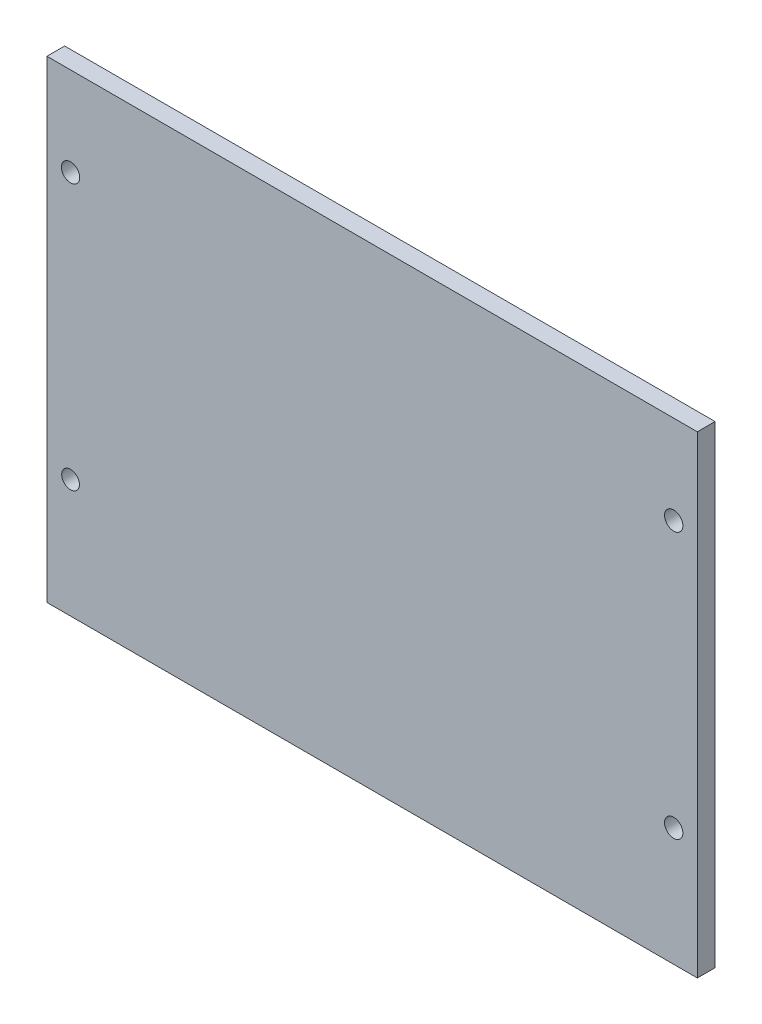
SolidWorks part; units mm, degrees
ref_plane "前视基准面" through (0, 0, 0) normal (0, 0, 1) x (1, 0, 0)
ref_plane "上视基准面" through (0, 0, 0) normal (0, 1, 0) x (1, 0, 0)
ref_plane "右视基准面" through (0, 0, 0) normal (1, 0, 0) x (0, 0, -1)
other "Configuration Table"
sketch "草图1" plane through (0, 0, 0) normal (0, 0, 1) x (1, 0, 0)
  line L1 (55, -40) -> (-55, -40)
  line L2 (55, -40) -> (55, 40)
  line L3 (55, 40) -> (-55, 40)
  line L4 (-55, -40) -> (-55, 40)
  line L5 (55, -40) -> (-55, 40) construction
  line L6 (55, 40) -> (-55, -40) construction
  point P0 (0, 0)
  dimension "D1" = 80
  dimension "D2" = 110
extrude "凸台-拉伸1" add sketch "草图1" along normal blind 3
sketch "草图2" plane through (0, 0, 3) normal (0, 0, 1) x (1, 0, 0)
  line L0 (55, 40) -> (-55, 40) construction
  line L1 (-55, 40) -> (-55, -40) construction
  line L2 (55, -40) -> (55, 40) construction
  line L3 (-55, -40) -> (55, -40) construction
  circle A0 centre (51, 25) radius 1.55
  circle A1 centre (51, -20) radius 1.55
  circle A2 centre (-51, 25) radius 1.55
  circle A3 centre (-51, -20) radius 1.5
  dimension "D1" = 15
  dimension "D2" = 15
  dimension "D3" = 4
  dimension "D4" = 4
  dimension "D5" = 4
  dimension "D6" = 20
  dimension "D7" = 20
  dimension "D8" = 4
extrude "切除-拉伸1" cut sketch "草图2" against normal blind 10
